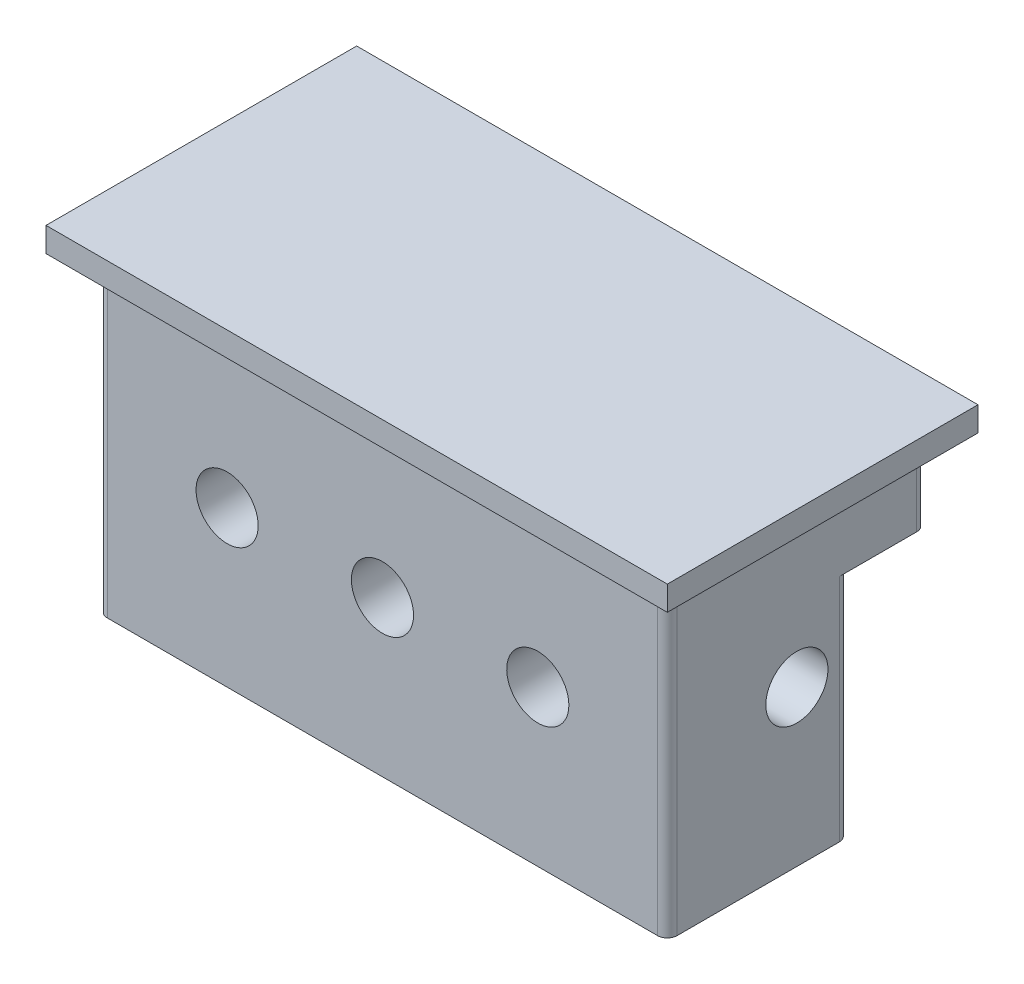
SolidWorks part; units mm, degrees
material "Nylon 101"
ref_plane "Front Plane" through (0, 0, 0) normal (0, 0, 1) x (1, 0, 0)
ref_plane "Top Plane" through (0, 0, 0) normal (0, 1, 0) x (1, 0, 0)
ref_plane "Right Plane" through (0, 0, 0) normal (1, 0, 0) x (0, 0, -1)
sketch "Sketch2" plane through (0, 0, 0) normal (0, 1, 0) x (1, 0, 0)
  line L1 (0, 0) -> (50.8, 0)
  line L2 (0, 0) -> (0, 25.4)
  line L3 (0, 25.4) -> (50.8, 25.4)
  line L12 (50.8, 0) -> (50.8, 25.4)
  line L14 (2.1082, 23.2918) -> (48.6918, 23.2918)
  line L15 (48.6918, 2.1082) -> (48.6918, 23.2918)
  line L16 (2.1082, 2.1082) -> (48.6918, 2.1082)
  line L17 (2.1082, 2.1082) -> (2.1082, 23.2918)
  dimension "D1" = 50.8
  dimension "D3" = 25.4
  dimension "D2" = 2.1082
extrude "Boss-Extrude2" add sketch "Sketch2" along normal blind 2 separate body contours L17 L16 L15 L14 | L16 L17 L14 L15 region at (0.568, 0, -12.7) region at (25.4, 0, -12.7)
extrude "Boss-Extrude3" add sketch "Sketch2<4>" against normal blind 25.4 contours L17 L16 L15 L14 region at (25.4, 0, -12.7)
sketch "Sketch2<4>" plane through (0, 0, 0) normal (0, 1, 0) x (1, 0, 0) same geometry as "Sketch2"
fillet "Fillet3" radius 0.7937 4 edges at (2.1082, -12.7, -23.2918) (48.6918, -12.7, -2.1082) (2.1082, -12.7, -2.1082) (48.6918, -12.7, -23.2918)
sketch "Sketch3" plane through (48.6918, 0, 0) normal (1, 0, 0) x (0, 0, -1)
  line L0 (2.902, 0) -> (22.498, 0) construction
  line L1 (2.902, -25.4) -> (22.498, -25.4) construction
  line L3 (12.7, 0) -> (12.7, -25.4) construction
  circle A0 centre (12.7, -12.7) radius 2.54
  dimension "D3" = 5.08
  dimension "D1" = 12.7
extrude "Cut-Extrude1" cut sketch "Sketch3" against normal through all
sketch "Sketch4" plane through (0, 0, -23.2918) normal (0, 0, -1) x (-1, 0, 0)
  line L0 (-47.898, -12.7) -> (-2.902, -12.7) construction
  line L1 (-47.898, 0) -> (-47.898, -25.4) construction
  line L2 (-2.902, -25.4) -> (-2.902, 0) construction
  line L3 (-2.902, 0) -> (-47.898, 0) construction
  circle A0 centre (-25.4, -12.7) radius 2.54
  circle A1 centre (-38.1, -12.7) radius 2.54
  circle A2 centre (-12.7, -12.7) radius 2.54
  dimension "D2" = 5.08
  dimension "D1" = 12.7
  dimension "D3" = 12.7
  dimension "D4" = 12.7
extrude "Cut-Extrude2" cut sketch "Sketch4" against normal through all
sketch "Sketch5" plane through (0, 0, -23.2918) normal (0, 0, -1) x (-1, 0, 0)
  line L1 (-48.6918, -25.4) -> (-2.1082, -25.4)
  line L2 (-48.6918, -25.4) -> (-48.6918, -6.604)
  line L3 (-48.6918, -6.604) -> (-2.1082, -6.604)
  line L4 (-2.1082, -25.4) -> (-2.1082, -6.604)
  line L5 (-48.6918, -25.4) -> (-48.6918, 0) construction
  line L6 (-2.1082, 0) -> (-2.1082, -25.4) construction
  line L7 (0, 0) -> (-50.8, 0) construction
  line L8 (-2.902, -25.4) -> (-47.898, -25.4) construction
  dimension "D1" = 6.604
extrude "Cut-Extrude3" cut sketch "Sketch5" against normal blind 6.35
fillet "Fillet4" radius 0.762 2 edges at (48.6918, -16.002, -16.9418) (2.1082, -16.002, -16.9418)
equation "\"D2@Sketch2\"=0.063+0.02"
